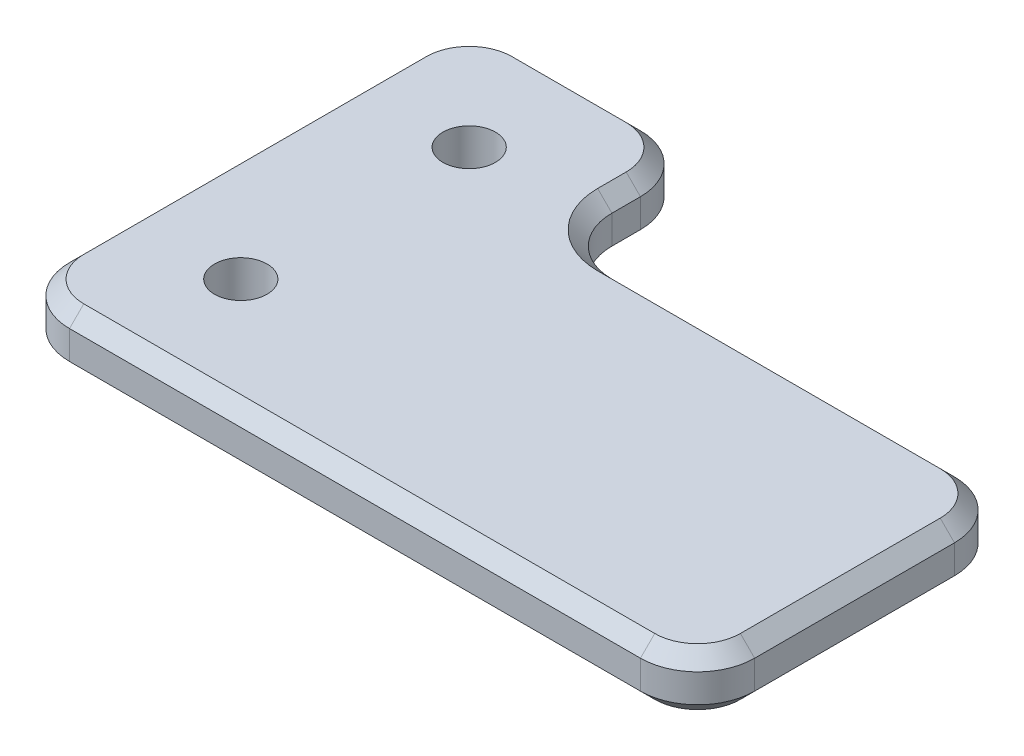
SolidWorks part; units mm, degrees
ref_plane "Front Plane" through (0, 0, 0) normal (0, 0, 1) x (1, 0, 0)
ref_plane "Top Plane" through (0, 0, 0) normal (0, 1, 0) x (1, 0, 0)
ref_plane "Right Plane" through (0, 0, 0) normal (1, 0, 0) x (0, 0, -1)
sketch "Sketch1" plane through (0, 0, 0) normal (0, 0, 1) x (1, 0, 0)
  line L13 (0, 0) -> (76.2, 0)
  line L14 (0, 0) -> (0, 6.35)
  line L15 (0, 6.35) -> (76.2, 6.35)
  line L16 (76.2, 0) -> (76.2, 6.35)
  dimension "D1" = 76.2
  dimension "D2" = 6.35
extrude "Boss-Extrude1" add sketch "Sketch1" along normal mid plane 50.8
sketch "Sketch2" plane through (0, 6.35, 0) normal (0, 1, 0) x (1, 0, 0)
  line L0 (76.2, 0) -> (0, 0) construction
  line L1 (76.2, -25.4) -> (76.2, 25.4) construction
  line L2 (0, -25.4) -> (0, 25.4) construction
  circle A0 centre (12.7, 12.7) radius 2.921
  circle A1 centre (12.7, -12.7) radius 2.921
  dimension "D1" = 5.842
  dimension "D2" = 12.7
  dimension "D3" = 12.7
extrude "Cut-Extrude1" cut sketch "Sketch2" against normal through all
sketch "Sketch3" plane through (0, 6.35, 0) normal (0, 1, 0) x (1, 0, 0)
  line L0 (0, -25.4) -> (0, 25.4) construction
  line L1 (76.2, 25.4) -> (25.4, 25.4)
  line L2 (76.2, 25.4) -> (76.2, 9.525)
  line L3 (76.2, 9.525) -> (25.4, 9.525)
  line L4 (25.4, 25.4) -> (25.4, 9.525)
  dimension "D1" = 25.4
  dimension "D2" = 15.875
extrude "Cut-Extrude2" cut sketch "Sketch3" against normal through all
fillet "Fillet1" radius 6.35 6 edges at (0, 3.175, 25.4) (0, 3.175, -25.4) (25.4, 3.175, -25.4) (25.4, 3.175, -9.525) (76.2, 3.175, 25.4) (76.2, 3.175, -9.525)
chamfer "Chamfer2" distance 1.5875 angle 45 24 edges at (1.8599, 0, 23.5401) (38.1, 0, 25.4) (74.3401, 0, 23.5401) (76.2, 0, 7.9375) (74.3401, 0, -7.6651) (50.8, 0, -9.525) (27.2599, 0, -11.3849) (25.4, 0, -17.4625) (23.5401, 0, -23.5401) (12.7, 0, -25.4) (0, 0, 0) (1.8599, 0, -23.5401) (1.8599, 6.35, 23.5401) (38.1, 6.35, 25.4) (74.3401, 6.35, 23.5401) (76.2, 6.35, 7.9375) (74.3401, 6.35, -7.6651) (50.8, 6.35, -9.525) (27.2599, 6.35, -11.3849) (25.4, 6.35, -17.4625) (23.5401, 6.35, -23.5401) (12.7, 6.35, -25.4) (1.8599, 6.35, -23.5401) (0, 6.35, 0)
